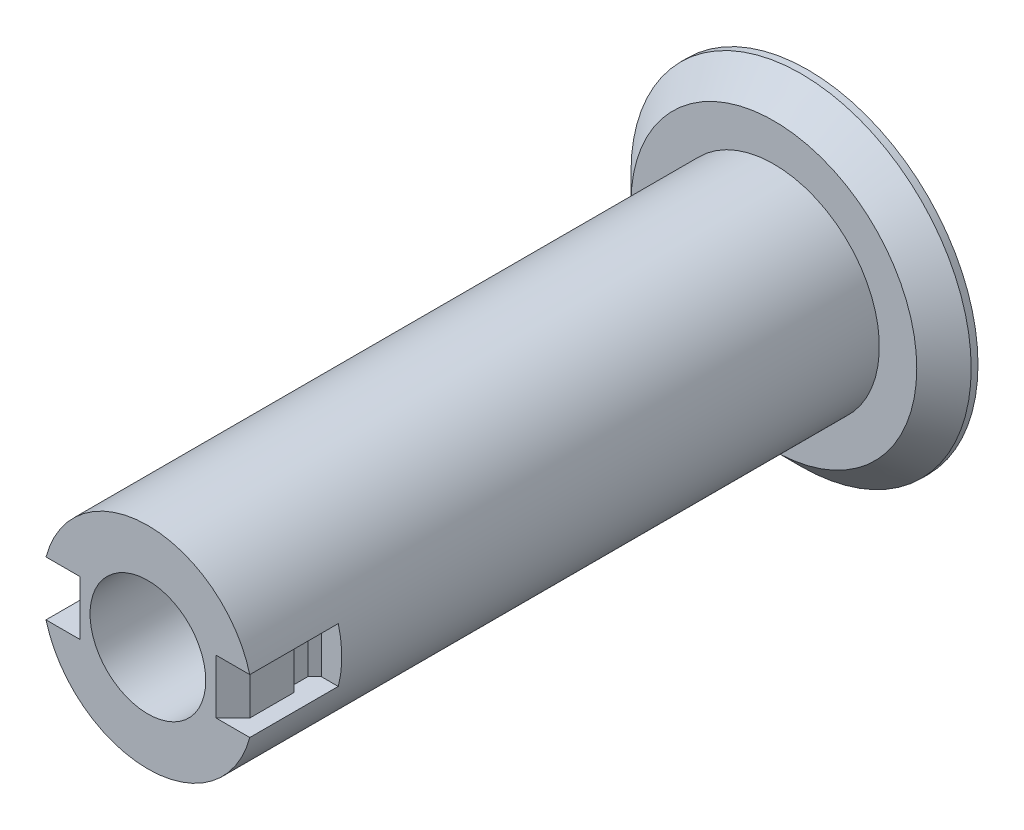
SolidWorks part; units mm, degrees
ref_plane "Front" through (0, 0, 0) normal (0, 0, 1) x (1, 0, 0)
ref_plane "Top" through (0, 0, 0) normal (0, 1, 0) x (1, 0, 0)
ref_plane "Right" through (0, 0, 0) normal (1, 0, 0) x (0, 0, -1)
sketch "Axle base sketch" plane through (0, 0, 0) normal (0, 0, 1) x (1, 0, 0)
  circle A0 centre (0, 0) radius 15.5
  dimension "D1" = 31
extrude "Axle" add sketch "Axle base sketch" along normal blind 92
sketch "Guard base" plane through (0, 0, 0) normal (0, 0, -1) x (-1, 0, 0)
  circle A0 centre (0, 0) radius 25
  dimension "D1" = 50
extrude "Guard" add sketch "Guard base" along normal blind 5
sketch "Inner axle hole base" plane through (0, 0, 92) normal (0, 0, 1) x (1, 0, 0)
  circle A0 centre (0, 0) radius 8.5
  dimension "D1" = 17
extrude "Inner axle hole" cut sketch "Inner axle hole base" against normal through all
sketch "Coupling tooth base" plane through (0, 0, 0) normal (0, 1, 0) x (1, 0, 0)
  line L0 (10, -92) -> (15.5, -92)
  line L1 (15.5, -92) -> (15.5, -79)
  line L2 (15.5, -92) -> (15.5, 0) construction
  line L3 (15.5, -79) -> (12.5, -79)
  line L5 (11.5, -82) -> (12.5, -83)
  line L6 (12.5, -83) -> (12.5, -89.5)
  line L7 (12.5, -89.5) -> (10, -92)
  line L9 (12.5, -79) -> (11.5, -80)
  line L10 (11.5, -80) -> (11.5, -82)
  dimension "D1" = 1
  dimension "D2" = 5.5
  dimension "D3" = 4
  dimension "D4" = 13
  dimension "D5" = 4
  dimension "D7" = 135
  dimension "D8" = 135
extrude "Coupling tooth hole" cut sketch "Coupling tooth base" against normal blind 4 and the other way blind 4 contours L9 L10 L5 L6 L7 L0 L1 L3 region at (13.7091, 0, 85.5933)
mirror "Coupling teeth" about plane through (0, 0, 0) normal (1, 0, 0) of "Coupling tooth hole"
chamfer "Uncoupling finger room" distance 4 angle 45 1 edges at (-25, 0, 0)
equation "\"32_92_spool_inner_diameter\"=32"
equation "\"D1@Axle base sketch\"=\"32_92_spool_inner_diameter\"- \"spool_inner_diameter_room\""
equation "\"spool_inner_diameter_room\"=1"
equation "\"32_92_spool_thickness\"=92"
equation "\"D1@Axle\"=\"32_92_spool_thickness\""
equation "\"32_92_guard_diameter\"=50"
equation "\"D1@Guard base\"=\"32_92_guard_diameter\""
equation "\"guard_thickness\"=5"
equation "\"D1@Guard\"=\"guard_thickness\""
equation "\"D1@Inner axle hole base\" = \"small_inner_axle_diameter\""
equation "\"32_92_coupling_tooth_height\"=13"
equation "\"D4@Coupling tooth base\"=\"32_92_coupling_tooth_height\""
equation "\"32_92_coupling_tooth_thickness_total\"=4"
equation "\"D3@Coupling tooth base\"=\"32_92_coupling_tooth_thickness_total\""
equation "\"32_92_coupling_tooth_protrusion\"=1"
equation "\"D1@Coupling tooth base\"=\"32_92_coupling_tooth_protrusion\""
equation "\"32_92_coupling_tooth_depth\"=8"
equation "\"D1@Coupling tooth hole\"=\"32_92_coupling_tooth_depth\"/2"
equation "\"D2@Coupling tooth hole\"=\"32_92_coupling_tooth_depth\"/2"
equation "\"32_92_coupling_tooth_base_thickness\"=5.5"
equation "\"D2@Coupling tooth base\"=\"32_92_coupling_tooth_base_thickness\""
equation "\"32_92_coupling_tooth_head_height\"=4"
equation "\"D5@Coupling tooth base\"=\"32_92_coupling_tooth_head_height\""
equation "\"small_inner_axle_diameter\"=17"
equation "\"D1@Uncoupling finger room\"=\"guard_thickness\"-1"
